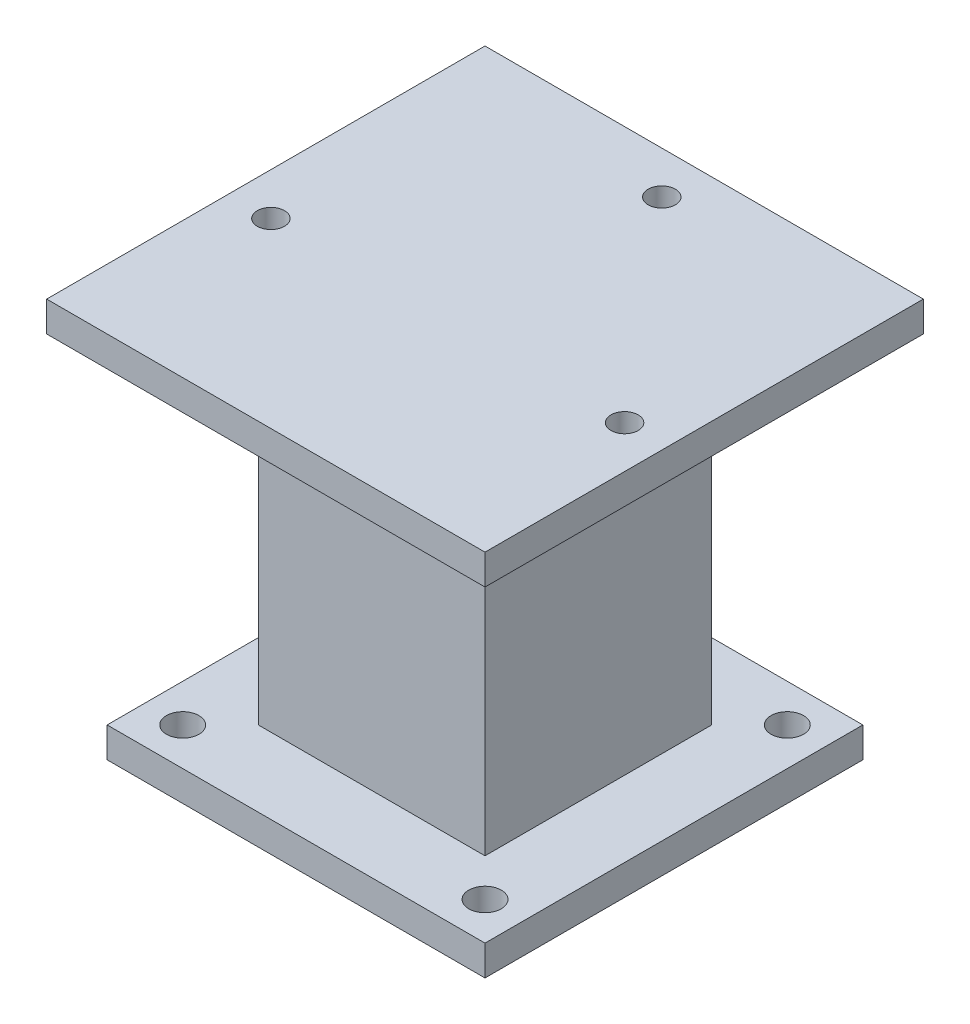
SolidWorks part; units mm, degrees
ref_plane "Front Plane" through (0, 0, 0) normal (0, 0, 1) x (1, 0, 0)
ref_plane "Top Plane" through (0, 0, 0) normal (0, 1, 0) x (1, 0, 0)
ref_plane "Right Plane" through (0, 0, 0) normal (1, 0, 0) x (0, 0, -1)
sketch "SK_Base" plane through (0, 0, 0) normal (0, 1, 0) x (1, 0, 0)
  line L1 (-25, 25) -> (25, 25)
  line L2 (-25, 25) -> (-25, -25)
  line L3 (-25, -25) -> (25, -25)
  line L4 (25, 25) -> (25, -25)
  dimension "D1" = 50
  dimension "D2" = 50
  dimension "D3" = 25
  dimension "D4" = 25
extrude "EX_Base" add sketch "SK_Base" along normal blind 4
sketch "SK_DeckHoles" plane through (0, 0, 0) normal (0, 1, 0) x (1, 0, 0)
  circle A0 centre (20, -20) radius 2.15
  circle A1 centre (-20, -20) radius 2.15
  circle A2 centre (20, 20) radius 2.15
  circle A3 centre (-20, 20) radius 2.15
  dimension "D3" = 4.3
  dimension "D6" = 4.3
  dimension "D9" = 4.3
  dimension "D12" = 4.3
  dimension "D1" = 20
  dimension "D2" = 20
  dimension "D4" = 20
  dimension "D5" = 20
  dimension "D7" = 20
  dimension "D8" = 20
  dimension "D10" = 20
  dimension "D11" = 20
extrude "CUT_DeckHoles" cut sketch "SK_DeckHoles" along normal blind 4
ref_plane "PL_Zp4" through (0, 4, 0) normal (0, 1, 0) x (1, 0, 0)
sketch "SK_Column" plane through (0, 4, 0) normal (0, 1, 0) x (1, 0, 0)
  line L1 (-15, 15) -> (15, 15)
  line L2 (-15, 15) -> (-15, -15)
  line L3 (-15, -15) -> (15, -15)
  line L4 (15, 15) -> (15, -15)
  dimension "D1" = 30
  dimension "D2" = 30
  dimension "D3" = 15
  dimension "D4" = 15
extrude "EX_Column" add sketch "SK_Column" along normal blind 44.8
ref_plane "PL_Zp48_8" through (0, 48.8, 0) normal (0, 1, 0) x (1, 0, 0)
sketch "SK_Top" plane through (0, 48.8, 0) normal (0, 1, 0) x (1, 0, 0)
  line L1 (-29, 29) -> (29, 29)
  line L2 (-29, 29) -> (-29, -29)
  line L3 (-29, -29) -> (29, -29)
  line L4 (29, 29) -> (29, -29)
  dimension "D1" = 58
  dimension "D2" = 58
  dimension "D3" = 29
  dimension "D4" = 29
extrude "EX_Top" add sketch "SK_Top" along normal blind 4
ref_plane "PL_Zp52_8" through (0, 52.8, 0) normal (0, 1, 0) x (1, 0, 0)
sketch "SK_Inserts_M25" plane through (0, 52.8, 0) normal (0, 1, 0) x (1, 0, 0)
  circle A0 centre (23.4, -4.93) radius 1.8
  circle A1 centre (-23.4, -4.93) radius 1.8
  circle A2 centre (0, 23.39) radius 1.8
  dimension "D3" = 3.6
  dimension "D6" = 3.6
  dimension "D8" = 3.6
  dimension "D1" = 4.93
  dimension "D2" = 23.4
  dimension "D4" = 4.93
  dimension "D5" = 23.4
  dimension "D7" = 23.39
extrude "CUT_Inserts_M25" cut sketch "SK_Inserts_M25" against normal blind 4
ref_axis "AX_X" through (0, 0, -31.9) along (0, 0, 1)
ref_axis "AX_Y" through (31.9, 0, 0) along (-1, 0, 0)
ref_axis "AX_Z" through (0, 55.44, 0) along (0, -1, 0)
sketch "SK_F_IF_Lidar" plane through (0, 52.8, 0) normal (0, 1, 0) x (1, 0, 0)
  point P0 (0, 0)
equation "\"BODY_L\"= 420"
equation "\"BODY_W\"= 340"
equation "\"FLOOR_Z\"= 35"
equation "\"DECK_Z\"= 180"
equation "\"DECK_T\"= 2"
equation "\"GRID\"= 20"
equation "\"PROFILE\"= 20"
equation "\"SM_T\"= 1.5"
equation "\"PAN_T\"= 1.5"
equation "\"PAN_TOP\"= \"FLOOR_Z\" + \"PAN_T\""
equation "\"RAIL_Y\"= 140"
equation "\"RAIL_X\"= \"BODY_L\" / 2 - \"PROFILE\" / 2 - 2"
equation "\"BOTRING_Z\"= \"PAN_TOP\" + \"PROFILE\" / 2"
equation "\"TOPRING_Z\"= \"DECK_Z\" - \"DECK_T\" - \"PROFILE\" / 2"
equation "\"DRAWER_Z\"= 93"
equation "\"MIDX_Z\"= \"DRAWER_Z\" - \"SM_T\" - \"PROFILE\" / 2"
equation "\"SKIN_Y\"= \"RAIL_Y\" + \"PROFILE\" / 2"
equation "\"SKIN_T\"= 2"
equation "\"WHEEL_D\"= 144"
equation "\"WHEEL_W\"= 52"
equation "\"TRACK\"= 365"
equation "\"AXLE_Z\"= \"WHEEL_D\" / 2"
equation "\"WHEEL_WEB_OFF\"= 6"
equation "\"HUB_T\"= 8"
equation "\"BUSHING_L\"= 6"
equation "\"HUB_GAP\"= 1"
equation "\"MOTOR_UP\"= 7"
equation "\"MOTOR_FACE_Y\"= \"TRACK\" / 2 + \"WHEEL_WEB_OFF\" - (\"BUSHING_L\" + \"HUB_GAP\" + \"HUB_T\")"
equation "\"MOTOR_AXIS_Z\"= \"AXLE_Z\" + \"MOTOR_UP\""
equation "\"CASTER_D\"= 50"
equation "\"CASTER_X\"= 150"
equation "\"CASTER_H\"= 68"
equation "\"POST_X\"= -40"
equation "\"POST_DY\"= 120"
equation "\"POST_SIZE\"= 20"
equation "\"POST_TOP\"= 400"
equation "\"BRACE_Z\"= 335"
equation "\"STRUT_X0\"= -140"
equation "\"HEAD_X0\"= -110"
equation "\"HEAD_X1\"= 12"
equation "\"BEZEL_T\"= 3"
equation "\"WEDGE_MID\"= 7.7"
equation "\"OAK_D\"= 22.9"
equation "\"HEAD_W\"= 210"
equation "\"HEAD_Z0\"= \"POST_TOP\""
equation "\"HEAD_TOP\"= 525"
equation "\"HEAD_TOP_X\"= -20"
equation "\"SCREEN_ANG\"= 35"
equation "\"LENS_X\"= 45.6"
equation "\"LENS_Z\"= 450"
equation "\"OAK_TILT\"= 5"
equation "\"OAK_VFOV_DEPTH\"= 79.5"
equation "\"OAK_VFOV_RGB\"= 72"
equation "\"LIDAR_X\"= 110"
equation "\"SCAN_Z\"= 260"
equation "\"STRUT_Z\"= \"SCAN_Z\" - 20"
equation "\"LIDAR_SCAN_H\"= 27.2"
equation "\"LIDAR_MOUNT_Z\"= \"SCAN_Z\" - \"LIDAR_SCAN_H\""
equation "\"ESTOP_X\"= -172.5"
equation "\"ESTOP_Y\"= -127.5"
equation "\"ESTOP_TOP\"= 225"
equation "\"BUMPER_T\"= 15"
equation "\"BUMPER_Z0\"= 40"
equation "\"BUMPER_Z1\"= 130"
equation "\"CLIFF_X\"= 218"
equation "\"CLIFF_Y\"= 105"
equation "\"CLIFF_Z\"= 72"
equation "\"CLIFF_ANG\"= 50"
equation "\"CONTACT_X\"= 216"
equation "\"CONTACT_Y\"= 64"
equation "\"CONTACT_Z\"= 30"
equation "\"DOCK_TAG_DIST\"= 250"
equation "\"DOCK_TAG_SIZE\"= 80"
equation "\"DOCK_TAG_Z\"= 400"
equation "\"BAT_L\"= 240"
equation "\"BAT_W\"= 90"
equation "\"BAT_H\"= 58"
equation "\"BAT_Z\"= \"DRAWER_Z\" + \"SM_T\""
equation "\"BAT_X\"= 0"
equation "\"PCB_L\"= 95"
equation "\"PCB_W\"= 120"
equation "\"PCB_H\"= 40"
equation "\"PCB_X\"= 62.5"
equation "\"DRV_X\"= 85"
equation "\"DRV_Y\"= 100"
equation "\"DRV_S\"= 50"
equation "\"COMPUTE_X\"= -65"
equation "\"COMPUTE_L\"= 90"
equation "\"COMPUTE_W\"= 160"
equation "\"D1@EX_Column\" = \"LIDAR_MOUNT_Z\" - \"DECK_Z\" - 8"
equation "\"D1@PL_Zp48_8\" = \"LIDAR_MOUNT_Z\" - \"DECK_Z\" - 4"
equation "\"D1@PL_Zp52_8\" = \"LIDAR_MOUNT_Z\" - \"DECK_Z\""
